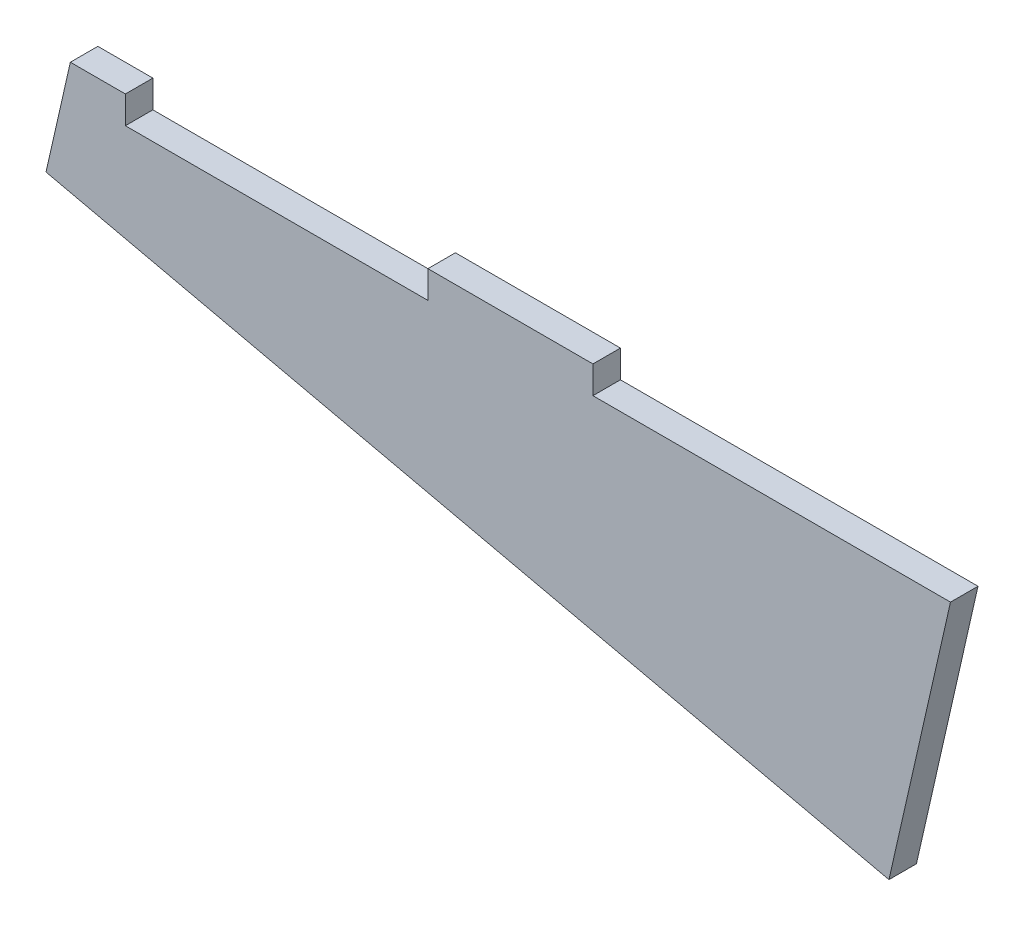
SolidWorks part; units mm, degrees
ref_plane "Front Plane" through (0, 0, 0) normal (0, 0, 1) x (1, 0, 0)
ref_plane "Top Plane" through (0, 0, 0) normal (0, 1, 0) x (1, 0, 0)
ref_plane "Right Plane" through (0, 0, 0) normal (1, 0, 0) x (0, 0, -1)
sketch "Sketch1" plane through (0, 0, 0) normal (0, 0, 1) x (1, 0, 0)
  line L0 (-186.4515, -43.5946) -> (-173.7515, -43.5946)
  line L4 (-173.7515, -43.5946) -> (-173.7515, -49.9446)
  line L5 (-173.7515, -49.9446) -> (-103.9015, -49.9446)
  line L6 (-103.9015, -49.9446) -> (-103.9015, -43.5946)
  line L7 (-103.9015, -43.5946) -> (-65.8015, -43.5946)
  line L8 (-65.8015, -43.5946) -> (-65.8015, -49.9446)
  line L9 (-65.8015, -49.9446) -> (16.7485, -49.9446)
  line L10 (16.7485, -49.9446) -> (2.5379, -112.5435)
  line L11 (2.5379, -112.5435) -> (-192.0745, -68.3643)
  line L12 (-192.0745, -68.3643) -> (-186.4515, -43.5946)
  line L13 (-1570.3632, 256.426) -> (-1176.6632, 167.0518) construction
  point P2 (-62.7286, -30.0583)
  dimension "D1" = 12.7
  dimension "D2" = 6.35
  dimension "D3" = 69.85
  dimension "D4" = 38.1
  dimension "D5" = 82.55
  dimension "D6" = 25.4
extrude "Boss-Extrude1" add sketch "Sketch1" against normal blind 6.35
